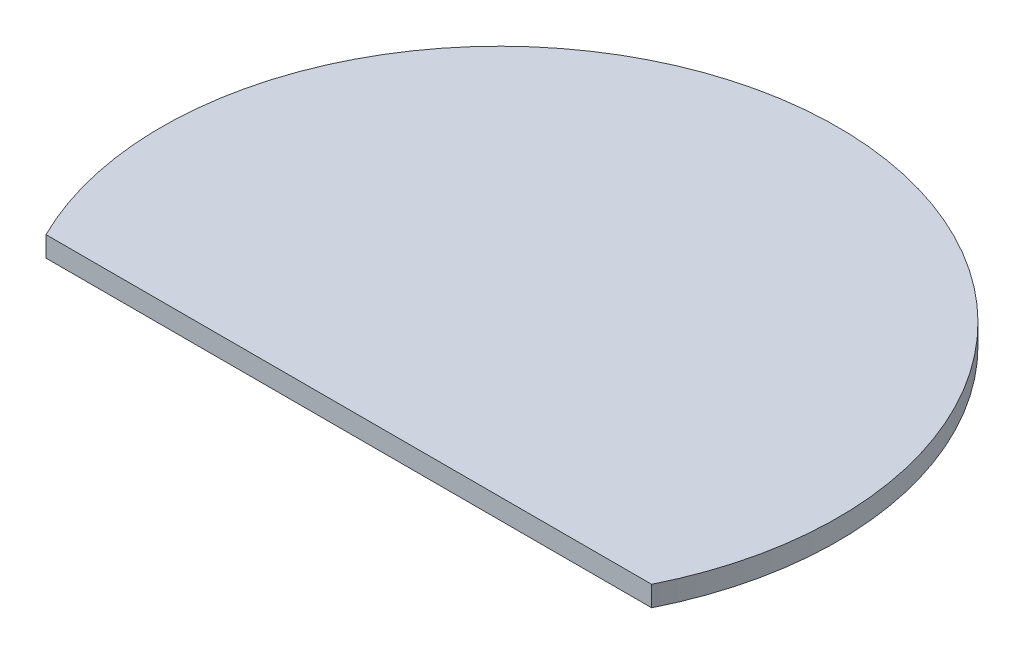
SolidWorks part; units mm, degrees
ref_plane "Front Plane" through (0, 0, 0) normal (0, 0, 1) x (1, 0, 0)
ref_plane "Top Plane" through (0, 0, 0) normal (0, 1, 0) x (1, 0, 0)
ref_plane "Right Plane" through (0, 0, 0) normal (1, 0, 0) x (0, 0, -1)
sketch "Sketch1" plane through (0, 0, 0) normal (0, 1, 0) x (1, 0, 0)
  line L0 (-14.8593, -7.4) -> (14.8593, -7.4)
  arc A0 (14.8593, -7.4) -> (-14.8593, -7.4) centre (0, 0) ccw
  dimension "D1" = 33.2
  dimension "D2" = 7.4
extrude "Boss-Extrude1" add sketch "Sketch1" along normal blind 1
